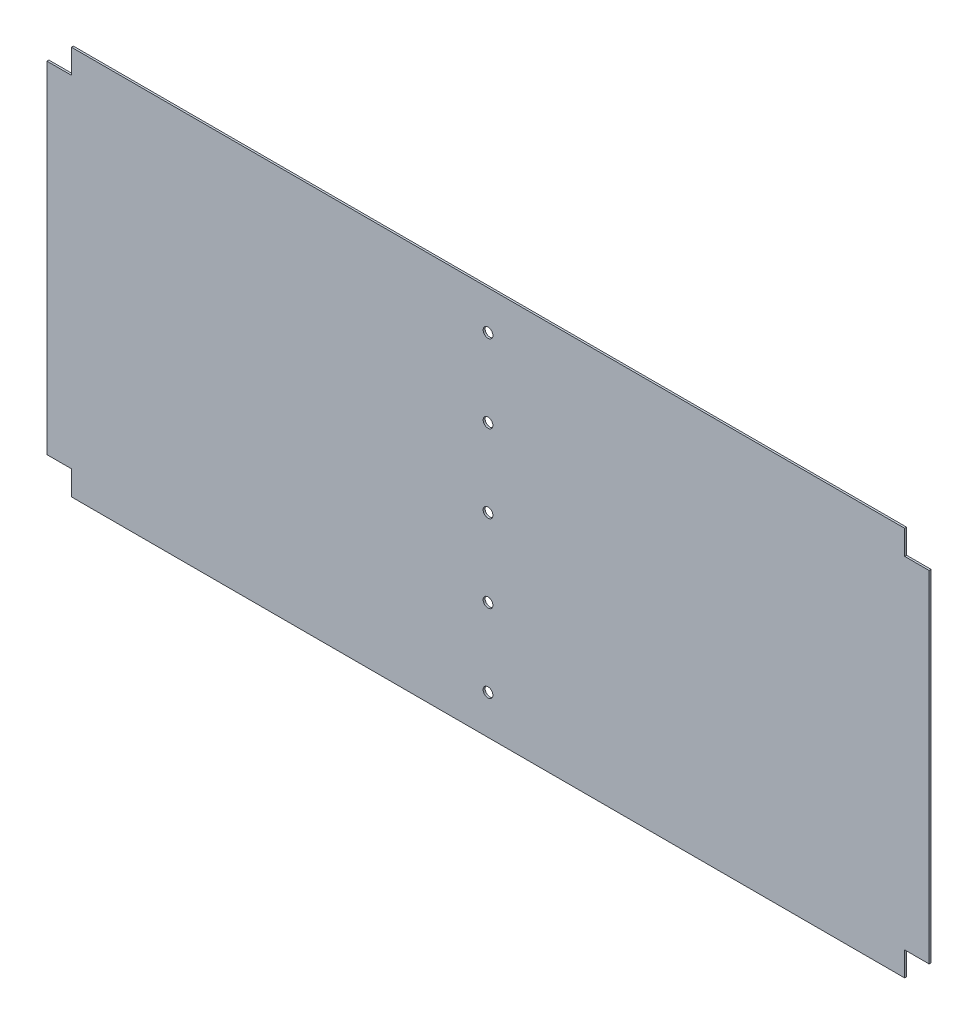
SolidWorks part; units mm, degrees
ref_plane "Front Plane" through (0, 0, 0) normal (0, 0, 1) x (1, 0, 0)
ref_plane "Top Plane" through (0, 0, 0) normal (0, 1, 0) x (1, 0, 0)
ref_plane "Right Plane" through (0, 0, 0) normal (1, 0, 0) x (0, 0, -1)
sketch "Çizim1" plane through (0, 0, 0) normal (0, 0, 1) x (1, 0, 0)
  line L1 (-453, 400) -> (453, 400)
  line L2 (-453, 400) -> (-453, 0)
  line L3 (-453, 0) -> (453, 0)
  line L4 (453, 400) -> (453, 0)
  point P4 (0, 0)
  dimension "D1" = 906
  dimension "D2" = 400
base flange "Taban-Flanş1" sketch "Çizim1" thickness 2 reverse thickness direction no parameters "D1"=0.7366
sketch "Çizim6" plane through (0, 0, 0) normal (0, 0, 1) x (1, 0, 0)
  line L0 (0, 0) -> (0, 141.4283) construction
  line L1 (-453, 400) -> (-428, 400)
  line L2 (-453, 400) -> (-453, 375)
  line L3 (-453, 375) -> (-428, 375)
  line L4 (-428, 400) -> (-428, 375)
  line L5 (-453, 200) -> (-327.7309, 200) construction
  line L6 (-453, 400) -> (-453, 0) construction
  line L7 (453, 400) -> (453, 375)
  line L8 (453, 400) -> (428, 400)
  line L9 (428, 400) -> (428, 375)
  line L10 (453, 375) -> (428, 375)
  line L11 (453, 25) -> (428, 25)
  line L12 (428, 0) -> (428, 25)
  line L13 (453, 0) -> (428, 0)
  line L14 (453, 0) -> (453, 25)
  line L15 (-428, 0) -> (-428, 25)
  line L16 (-453, 25) -> (-428, 25)
  line L17 (-453, 0) -> (-453, 25)
  line L18 (-453, 0) -> (-428, 0)
  dimension "D1" = 25
  dimension "D2" = 25
extrude "Kes-Ekstrüzyon1" cut sketch "Çizim6" against normal blind 10 normal cut yes
sketch "Çizim7" plane through (0, 0, 0) normal (0, 0, 1) x (1, 0, 0)
  line L0 (428, 400) -> (-428, 400) construction
  line L1 (453, 25) -> (453, 375) construction
  circle A0 centre (0, 360) radius 5
  circle A1 centre (0, 280) radius 5
  circle A2 centre (0, 200) radius 5
  circle A3 centre (0, 120) radius 5
  circle A4 centre (0, 40) radius 5
  dimension "D1" = 10
  dimension "D3" = 40
  dimension "D4" = 40
  dimension "D5" = 453
  dimension "D2" = 5
extrude "Kes-Ekstrüzyon2" cut sketch "Çizim7" against normal blind 10 normal cut yes
sketch "Büküm-Çizgileri1" [suppressed] plane through (0, 0, 0) normal (0, 1, 0) x (1, 0, 0)
sketch "Sınırlandırma-Kutusu1" [suppressed] plane through (0, 0, 0) normal (0, 1, 0) x (1, 0, 0)
sheet metal parameters "Sac-Levha1" thickness 2 parameters "D1"=0.7366
flat pattern "Düz-Çoğaltma1" [suppressed]
sketch "Büküm-Çizgileri2" plane through (0, 0, 0) normal (0, 1, 0) x (1, 0, 0)
sketch3d "Sınırlandırma-Kutusu2" [suppressed]
  line L0 (453, 0, 0) -> (-453, 0, 0) construction
  line L1 (453, 400, 0) -> (-453, 400, 0) construction
  line L2 (453, 0, 0) -> (453, 400, 0) construction
  line L3 (-453, 0, 0) -> (-453, 400, 0) construction
sheet metal parameters "Sac-Levha2" thickness 2 parameters "D1"=0.7366
flat pattern "Düz-Çoğaltma1"
sketch "Büküm-Çizgileri2" plane through (0, 0, 0) normal (0, 1, 0) x (1, 0, 0)
sketch3d "Sınırlandırma-Kutusu2" [suppressed]
  line L0 (-453, 0, 0) -> (453, 0, 0) construction
  line L1 (-453, 400, 0) -> (453, 400, 0) construction
  line L2 (-453, 0, 0) -> (-453, 400, 0) construction
  line L3 (453, 0, 0) -> (453, 400, 0) construction
sheet metal parameters "Sac-Levha3" thickness 2 parameters "D1"=0.7366
flat pattern "Düz-Çoğaltma1"
sketch "Büküm-Çizgileri2" plane through (0, 0, 0) normal (0, 1, 0) x (1, 0, 0)
sketch3d "Sınırlandırma-Kutusu2" [suppressed]
  line L0 (-453, 0, 0) -> (453, 0, 0) construction
  line L1 (-453, 400, 0) -> (453, 400, 0) construction
  line L2 (-453, 0, 0) -> (-453, 400, 0) construction
  line L3 (453, 0, 0) -> (453, 400, 0) construction
